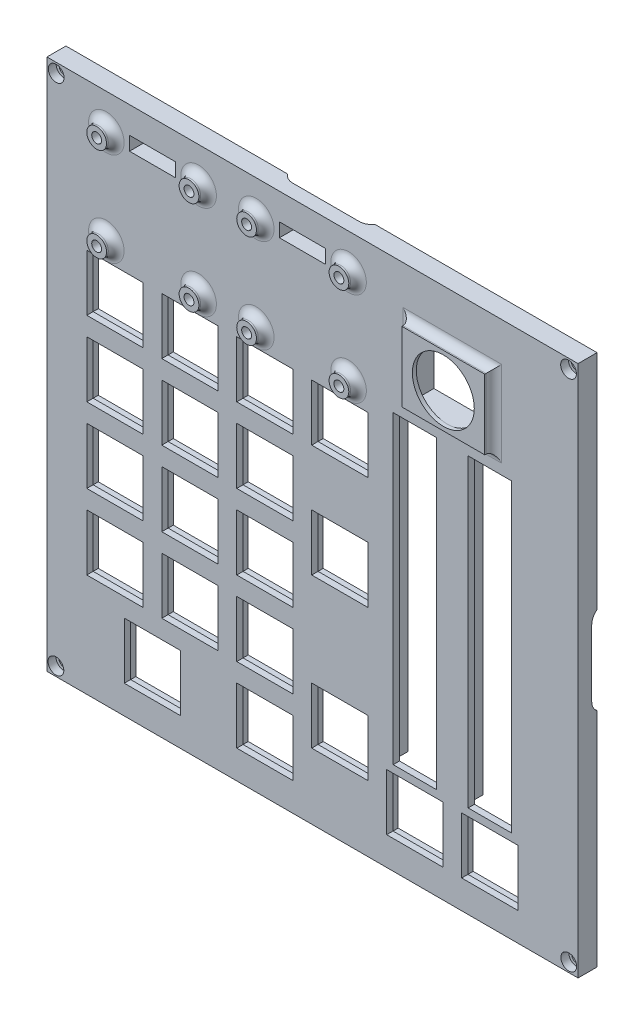
SolidWorks part; units mm, degrees
ref_plane "Front Plane" through (0, 0, 0) normal (0, 0, 1) x (1, 0, 0)
ref_plane "Top Plane" through (0, 0, 0) normal (0, 1, 0) x (1, 0, 0)
ref_plane "Right Plane" through (0, 0, 0) normal (1, 0, 0) x (0, 0, -1)
sketch "Sketch1" plane through (0, 0, 0) normal (0, 0, 1) x (1, 0, 0)
  line L0 (76.95, 30.15) -> (91.25, 30.15) construction
  line L1 (-63, 63) -> (63, 63)
  line L2 (-63, 63) -> (-63, -63)
  line L3 (-63, -63) -> (63, -63)
  line L4 (63, 63) -> (63, -63)
  line L5 (-57.15, 15.85) -> (-42.85, 15.85)
  line L6 (-57.15, 15.85) -> (-57.15, 30.15)
  line L7 (-57.15, 30.15) -> (-42.85, 30.15)
  line L8 (-42.85, 15.85) -> (-42.85, 30.15)
  line L9 (-57.15, 15.85) -> (-42.85, 30.15) construction
  line L10 (-57.15, 30.15) -> (-42.85, 15.85) construction
  line L11 (91.25, 30.15) -> (91.25, 15.85) construction
  line L12 (94.05, 32.05) -> (112.15, 32.05) construction
  line L13 (-59.05, 13.95) -> (-40.95, 13.95)
  line L14 (-59.05, 13.95) -> (-59.05, 32.05)
  line L15 (-59.05, 32.05) -> (-40.95, 32.05)
  line L16 (-40.95, 13.95) -> (-40.95, 32.05)
  line L17 (-59.05, 13.95) -> (-40.95, 32.05) construction
  line L18 (-59.05, 32.05) -> (-40.95, 13.95) construction
  line L19 (112.15, 32.05) -> (112.15, 13.95) construction
  line L20 (-38.15, 15.85) -> (-38.15, 30.15)
  line L21 (-38.15, 15.85) -> (-23.85, 15.85)
  line L22 (-38.15, 30.15) -> (-23.85, 30.15)
  line L23 (-23.85, 15.85) -> (-23.85, 30.15)
  line L24 (-40.05, 13.95) -> (-40.05, 32.05)
  line L25 (-40.05, 13.95) -> (-21.95, 13.95)
  line L26 (-21.95, 13.95) -> (-21.95, 32.05)
  line L27 (-40.05, 32.05) -> (-21.95, 32.05)
  line L28 (-19.15, 15.85) -> (-19.15, 30.15)
  line L29 (-19.15, 15.85) -> (-4.85, 15.85)
  line L30 (-19.15, 30.15) -> (-4.85, 30.15)
  line L31 (-4.85, 15.85) -> (-4.85, 30.15)
  line L32 (-21.05, 13.95) -> (-21.05, 32.05)
  line L33 (-21.05, 13.95) -> (-2.95, 13.95)
  line L34 (-2.95, 13.95) -> (-2.95, 32.05)
  line L35 (-21.05, 32.05) -> (-2.95, 32.05)
  line L36 (-38.15, -3.15) -> (-38.15, 11.15)
  line L37 (-38.15, -3.15) -> (-23.85, -3.15)
  line L38 (-38.15, 11.15) -> (-23.85, 11.15)
  line L39 (-23.85, -3.15) -> (-23.85, 11.15)
  line L40 (-40.05, -5.05) -> (-40.05, 13.05)
  line L41 (-40.05, -5.05) -> (-21.95, -5.05)
  line L42 (-21.95, -5.05) -> (-21.95, 13.05)
  line L43 (-40.05, 13.05) -> (-21.95, 13.05)
  line L44 (-19.15, -3.15) -> (-19.15, 11.15)
  line L45 (-19.15, -3.15) -> (-4.85, -3.15)
  line L46 (-19.15, 11.15) -> (-4.85, 11.15)
  line L47 (-4.85, -3.15) -> (-4.85, 11.15)
  line L48 (-21.05, -5.05) -> (-21.05, 13.05)
  line L49 (-21.05, -5.05) -> (-2.95, -5.05)
  line L50 (-2.95, -5.05) -> (-2.95, 13.05)
  line L51 (-21.05, 13.05) -> (-2.95, 13.05)
  line L52 (-38.15, -22.15) -> (-38.15, -7.85)
  line L53 (-38.15, -22.15) -> (-23.85, -22.15)
  line L54 (-38.15, -7.85) -> (-23.85, -7.85)
  line L55 (-23.85, -22.15) -> (-23.85, -7.85)
  line L56 (-40.05, -24.05) -> (-40.05, -5.95)
  line L57 (-40.05, -24.05) -> (-21.95, -24.05)
  line L58 (-21.95, -24.05) -> (-21.95, -5.95)
  line L59 (-40.05, -5.95) -> (-21.95, -5.95)
  line L60 (-19.15, -22.15) -> (-19.15, -7.85)
  line L61 (-19.15, -22.15) -> (-4.85, -22.15)
  line L62 (-19.15, -7.85) -> (-4.85, -7.85)
  line L63 (-4.85, -22.15) -> (-4.85, -7.85)
  line L64 (-21.05, -24.05) -> (-21.05, -5.95)
  line L65 (-21.05, -24.05) -> (-2.95, -24.05)
  line L66 (-2.95, -24.05) -> (-2.95, -5.95)
  line L67 (-21.05, -5.95) -> (-2.95, -5.95)
  line L68 (-38.15, -41.15) -> (-38.15, -26.85)
  line L69 (-38.15, -41.15) -> (-23.85, -41.15)
  line L70 (-38.15, -26.85) -> (-23.85, -26.85)
  line L71 (-23.85, -41.15) -> (-23.85, -26.85)
  line L72 (-40.05, -43.05) -> (-40.05, -24.95)
  line L73 (-40.05, -43.05) -> (-21.95, -43.05)
  line L74 (-21.95, -43.05) -> (-21.95, -24.95)
  line L75 (-40.05, -24.95) -> (-21.95, -24.95)
  line L76 (-19.15, -41.15) -> (-19.15, -26.85)
  line L77 (-19.15, -41.15) -> (-4.85, -41.15)
  line L78 (-19.15, -26.85) -> (-4.85, -26.85)
  line L79 (-4.85, -41.15) -> (-4.85, -26.85)
  line L80 (-21.05, -43.05) -> (-21.05, -24.95)
  line L81 (-21.05, -43.05) -> (-2.95, -43.05)
  line L82 (-2.95, -43.05) -> (-2.95, -24.95)
  line L83 (-21.05, -24.95) -> (-2.95, -24.95)
  line L84 (-57.15, -3.15) -> (-57.15, 11.15)
  line L85 (-57.15, -3.15) -> (-42.85, -3.15)
  line L86 (-57.15, 11.15) -> (-42.85, 11.15)
  line L87 (-42.85, -3.15) -> (-42.85, 11.15)
  line L88 (-59.05, -5.05) -> (-59.05, 13.05)
  line L89 (-59.05, -5.05) -> (-40.95, -5.05)
  line L90 (-40.95, -5.05) -> (-40.95, 13.05)
  line L91 (-59.05, 13.05) -> (-40.95, 13.05)
  line L92 (-57.15, -22.15) -> (-57.15, -7.85)
  line L93 (-57.15, -22.15) -> (-42.85, -22.15)
  line L94 (-57.15, -7.85) -> (-42.85, -7.85)
  line L95 (-42.85, -22.15) -> (-42.85, -7.85)
  line L96 (-59.05, -24.05) -> (-59.05, -5.95)
  line L97 (-59.05, -24.05) -> (-40.95, -24.05)
  line L98 (-40.95, -24.05) -> (-40.95, -5.95)
  line L99 (-59.05, -5.95) -> (-40.95, -5.95)
  line L100 (-57.15, -41.15) -> (-57.15, -26.85)
  line L101 (-57.15, -41.15) -> (-42.85, -41.15)
  line L102 (-57.15, -26.85) -> (-42.85, -26.85)
  line L103 (-42.85, -41.15) -> (-42.85, -26.85)
  line L104 (-59.05, -43.05) -> (-59.05, -24.95)
  line L105 (-59.05, -43.05) -> (-40.95, -43.05)
  line L106 (-40.95, -43.05) -> (-40.95, -24.95)
  line L107 (-59.05, -24.95) -> (-40.95, -24.95)
  line L108 (-19.15, -60.15) -> (-19.15, -45.85)
  line L109 (-19.15, -45.85) -> (-4.85, -45.85)
  line L110 (-4.85, -60.15) -> (-4.85, -45.85)
  line L111 (-19.15, -60.15) -> (-4.85, -60.15)
  line L112 (-21.05, -62.05) -> (-21.05, -43.95)
  line L113 (-21.05, -43.95) -> (-2.95, -43.95)
  line L114 (-2.95, -62.05) -> (-2.95, -43.95)
  line L115 (-21.05, -62.05) -> (-2.95, -62.05)
  line L116 (-0.15, 15.85) -> (-0.15, 30.15)
  line L117 (-0.15, 30.15) -> (14.15, 30.15)
  line L118 (14.15, 15.85) -> (14.15, 30.15)
  line L119 (-0.15, 15.85) -> (14.15, 15.85)
  line L120 (-2.05, 13.95) -> (-2.05, 32.05)
  line L121 (-2.05, 32.05) -> (16.05, 32.05)
  line L122 (16.05, 13.95) -> (16.05, 32.05)
  line L123 (-2.05, 13.95) -> (16.05, 13.95)
  line L124 (-0.15, -12.65) -> (-0.15, 1.65)
  line L125 (-0.15, 1.65) -> (14.15, 1.65)
  line L126 (14.15, -12.65) -> (14.15, 1.65)
  line L127 (-0.15, -12.65) -> (14.15, -12.65)
  line L128 (-2.05, -14.55) -> (-2.05, 3.55)
  line L129 (-2.05, 3.55) -> (16.05, 3.55)
  line L130 (16.05, -14.55) -> (16.05, 3.55)
  line L131 (-2.05, -14.55) -> (16.05, -14.55)
  line L132 (-0.15, -50.65) -> (-0.15, -36.35)
  line L133 (-0.15, -36.35) -> (14.15, -36.35)
  line L134 (14.15, -50.65) -> (14.15, -36.35)
  line L135 (-0.15, -50.65) -> (14.15, -50.65)
  line L136 (-2.05, -52.55) -> (-2.05, -34.45)
  line L137 (-2.05, -34.45) -> (16.05, -34.45)
  line L138 (16.05, -52.55) -> (16.05, -34.45)
  line L139 (-2.05, -52.55) -> (16.05, -52.55)
  line L140 (-47.65, -60.15) -> (-47.65, -45.85)
  line L141 (-47.65, -45.85) -> (-33.35, -45.85)
  line L142 (-33.35, -60.15) -> (-33.35, -45.85)
  line L143 (-47.65, -60.15) -> (-33.35, -60.15)
  line L144 (-49.55, -62.05) -> (-49.55, -43.95)
  line L145 (-49.55, -43.95) -> (-31.45, -43.95)
  line L146 (-31.45, -62.05) -> (-31.45, -43.95)
  line L147 (-49.55, -62.05) -> (-31.45, -62.05)
  line L148 (30, 32.3225) -> (22, 32.3225) construction
  line L149 (16.95, -62.05) -> (35.05, -62.05)
  line L150 (16.95, -62.05) -> (16.95, -43.95)
  line L151 (16.95, -43.95) -> (35.05, -43.95)
  line L152 (35.05, -62.05) -> (35.05, -43.95)
  line L153 (16.95, -62.05) -> (35.05, -43.95) construction
  line L154 (16.95, -43.95) -> (35.05, -62.05) construction
  line L155 (18.85, -60.15) -> (33.15, -60.15)
  line L156 (18.85, -60.15) -> (18.85, -45.85)
  line L157 (18.85, -45.85) -> (33.15, -45.85)
  line L158 (33.15, -60.15) -> (33.15, -45.85)
  line L159 (18.85, -60.15) -> (33.15, -45.85) construction
  line L160 (18.85, -45.85) -> (33.15, -60.15) construction
  line L161 (35.95, -62.05) -> (54.05, -62.05)
  line L162 (35.95, -62.05) -> (35.95, -43.95)
  line L163 (35.95, -43.95) -> (54.05, -43.95)
  line L164 (54.05, -62.05) -> (54.05, -43.95)
  line L165 (35.95, -62.05) -> (54.05, -43.95) construction
  line L166 (35.95, -43.95) -> (54.05, -62.05) construction
  line L167 (37.85, -60.15) -> (52.15, -60.15)
  line L168 (37.85, -60.15) -> (37.85, -45.85)
  line L169 (37.85, -45.85) -> (52.15, -45.85)
  line L170 (52.15, -60.15) -> (52.15, -45.85)
  line L171 (37.85, -60.15) -> (52.15, -45.85) construction
  line L172 (37.85, -45.85) -> (52.15, -60.15) construction
  line L173 (20.5, 33.3225) -> (31.5, 33.3225)
  line L174 (20.5, 33.3225) -> (20.5, -43.95)
  line L175 (20.5, -43.95) -> (31.5, -43.95)
  line L176 (31.5, 33.3225) -> (31.5, -43.95)
  line L177 (-45.83, 60.275) -> (-35.17, 60.275) construction
  line L178 (30.5, -10.1622) -> (30.5, -27.0779) construction
  line L179 (21.5, -10.1622) -> (21.5, -27.0779) construction
  line L180 (49, 32.3225) -> (41, 32.3225) construction
  line L181 (39.5, 33.3225) -> (50.5, 33.3225)
  line L182 (39.5, 33.3225) -> (39.5, -43.95)
  line L183 (39.5, -43.95) -> (50.5, -43.95)
  line L184 (50.5, 33.3225) -> (50.5, -43.95)
  line L185 (40.5, 30.2991) -> (40.5, 31.8225) construction
  line L186 (49.5, 31.8225) -> (49.5, 30.2991) construction
  line L187 (-46.33, 60.775) -> (-34.67, 60.775)
  line L188 (27, 50.3) -> (27, 48.3) construction
  line L189 (26, 38.95) -> (45, 38.95)
  line L190 (26, 38.95) -> (26, 54.65)
  line L191 (26, 54.65) -> (45, 54.65)
  line L192 (45, 38.95) -> (45, 54.65)
  line L193 (26, 38.95) -> (45, 54.65) construction
  line L194 (26, 54.65) -> (45, 38.95) construction
  line L195 (37, 53.65) -> (34, 53.65) construction
  line L196 (19.5, 34.3225) -> (32.5, 34.3225)
  line L197 (19.5, 34.3225) -> (19.5, -43.95)
  line L198 (19.5, -43.95) -> (32.5, -43.95)
  line L199 (32.5, 34.3225) -> (32.5, -43.95)
  line L200 (38.5, 34.3225) -> (51.5, 34.3225)
  line L201 (38.5, 34.3225) -> (38.5, -43.95)
  line L202 (38.5, -43.95) -> (51.5, -43.95)
  line L203 (51.5, 34.3225) -> (51.5, -43.95)
  line L204 (-46.33, 60.775) -> (-46.33, 57.275)
  line L205 (-46.33, 57.275) -> (-34.67, 57.275)
  line L206 (-34.67, 60.775) -> (-34.67, 57.275)
  line L207 (-8.33, 60.775) -> (3.33, 60.775)
  line L208 (-8.33, 60.775) -> (-8.33, 57.275)
  line L209 (-8.33, 57.275) -> (3.33, 57.275)
  line L210 (3.33, 60.775) -> (3.33, 57.275)
  line L211 (-45.83, 57.775) -> (-35.17, 57.775) construction
  line L212 (-35.17, 60.025) -> (-35.17, 58.025) construction
  line L213 (-45.83, 60.025) -> (-45.83, 58.025) construction
  line L214 (2.83, 60.025) -> (2.83, 58.025) construction
  line L215 (-7.83, 60.275) -> (2.83, 60.275) construction
  line L216 (-7.83, 60.025) -> (-7.83, 58.025) construction
  line L217 (-7.83, 57.775) -> (2.83, 57.775) construction
  circle A0 centre (-50, 23) radius 1.1145 construction
  circle A1 centre (26, -53) radius 1.1245 construction
  circle A2 centre (45, -53) radius 1.0254 construction
  circle A3 centre (35.5, 46.8) radius 3.3 construction
  circle A4 centre (35.5, 46.8) radius 3.3 construction
  circle A5 centre (35.5, 46.8) radius 7.85
  circle A6 centre (-52.2, 58.5) radius 1.25
  circle A7 centre (-28.8, 58.5) radius 1.25
  circle A8 centre (-52.2, 34.7) radius 1.25
  circle A9 centre (-28.8, 34.7) radius 1.25
  circle A10 centre (-14.2, 34.7) radius 1.25
  circle A11 centre (-14.2, 58.5) radius 1.25
  circle A12 centre (9.2, 58.5) radius 1.25
  circle A13 centre (9.2, 34.7) radius 1.25
  ellipse E0 centre (26, -53) end of major axis (27.995, -53) minor radius 1.995 construction
  ellipse E1 centre (-50, 23) end of major axis (-50, 21.005) minor radius 1.995 construction
  ellipse E2 centre (45, -53) end of major axis (45, -54.995) minor radius 1.995 construction
  ellipse E3 centre (-52.2, 58.5) end of major axis (-52.2, 57.5) minor radius 1 construction
  ellipse E4 centre (-52.2, 34.7) end of major axis (-52.2, 33.7) minor radius 1 construction
  ellipse E5 centre (-28.8, 34.7) end of major axis (-28.8, 33.7) minor radius 1 construction
  ellipse E6 centre (-14.2, 58.5) end of major axis (-14.2, 57.5) minor radius 1 construction
  ellipse E7 centre (9.2, 58.5) end of major axis (9.2, 57.5) minor radius 1 construction
  ellipse E8 centre (9.2, 34.7) end of major axis (9.2, 33.7) minor radius 1 construction
  ellipse E9 centre (-14.2, 34.7) end of major axis (-14.2, 33.7) minor radius 1 construction
  ellipse E10 centre (-28.8, 58.5) end of major axis (-28.8, 57.5) minor radius 1 construction
  point P212 (35.5, 46.8)
  dimension "D23" = 15.7
  dimension "D38" = 2.5
  dimension "D3" = 19
  dimension "D4" = 19
  dimension "D6" = 19
  dimension "D8" = 19
  dimension "D10" = 28.5
  dimension "D12" = 38
  dimension "D14" = 28.5
  dimension "D15" = 1
  dimension "D16" = 1
  dimension "D17" = 1
  dimension "D18" = 1
  dimension "D19" = 1
  dimension "D20" = 1
  dimension "D21" = 1
  dimension "D22" = 1
  dimension "D24" = 1
  dimension "D25" = 1
  dimension "D26" = 1
  dimension "D27" = 1
  dimension "D28" = 1
  dimension "D29" = 1
  dimension "D30" = 0.5
  dimension "D31" = 0.5
  dimension "D32" = 0.5
  dimension "D33" = 0.5
  dimension "D34" = 0.5
  dimension "D35" = 0.5
  dimension "D36" = 0.5
  dimension "D37" = 0.5
  dimension "D1" = 3
  dimension "D2" = 4
  dimension "D5" = 2
  dimension "D7" = 2
  dimension "D9" = 2
  dimension "D11" = 2
  dimension "D13" = 2
extrude "Boss-Extrude1" add sketch "Sketch1" along normal up to surface (3.2116 mm away) contours L4 L1 L2 L3 L192 L189 L190 L191 L147 L144 L145 L146 L139 L136 L137 L138 L131 L128 L129 L130 L123 L120 L121 L122 L115 L112 L113 L114 L96 L99 L98 L97 L80 L83 L82 L81 L64 L67 L66 L65 region at (3.9869, 12.3357, 0)
extrude "Boss-Extrude2" add sketch "Sketch1<4>" along normal up to surface (1.6 mm away) from surface contours L4 L1 L2 L3 L192 L189 L190 L191 L147 L144 L145 L146 L139 L136 L137 L138 L131 L128 L129 L130 L123 L120 L121 L122 L115 L112 L113 L114 L96 L99 L98 L97 L80 L83 L82 L81 L64 L67 L66 L65 | L120 L123 L122 L121 L119 L116 L117 L118 | L27 L24 L25 L26 L23 L21 L20 L22 | L43 L40 L41 L42 L39 L37 L36 L38 | L51 L48 L49 L50 L47 L45 L44 L46 | L35 L32 L33 L34 L31 L29 L28 L30 | L91 L88 L89 L90 L87 L85 L84 L86 | L13 L16 L15 L14 L8 L5 L6 L7 | L59 L56 L57 L58 L55 L53 L52 L54 | L99 L96 L97 L98 L95 L93 L92 L94 | L67 L64 L65 L66 L63 L61 L60 L62 | L107 L104 L105 L106 L103 L101 L100 L102 | L75 L72 L73 L74 L71 L69 L68 L70 | L83 L80 L81 L82 L79 L77 L76 L78 | L144 L147 L146 L145 L143 L140 L141 L142 | L112 L115 L114 L113 L111 L108 L109 L110 | L136 L139 L138 L137 L135 L132 L133 L134 | L128 L131 L130 L129 L127 L124 L125 L126 | L149 L152 L151 L150 L158 L155 L156 L157 | L161 L164 L163 L162 L170 L167 L168 L169 | L199 L196 L197 L151 L174 L173 L176 | L203 L200 L201 L163 L182 L181 L184 region at (3.9869, 12.3357, 0) region at (-58.794, 23, 0) region at (-39.794, 23, 0) region at (-20.794, 23, 0) region at (-39.794, 4, 0) region at (-20.794, 4, 0) region at (-39.794, -15, 0) region at (-20.794, -15, 0) region at (-39.794, -34, 0) region at (-20.794, -34, 0) region at (-58.794, 4, 0) region at (-58.794, -15, 0) region at (-58.794, -34, 0) region at (-20.794, -53, 0) region at (-1.794, 23, 0) region at (-1.794, -5.5, 0) region at (-1.794, -43.5, 0) region at (-49.294, -53, 0) region at (17.206, -53, 0) region at (20.2934, -4.8138, 0) region at (36.206, -53, 0) region at (39.2934, -4.8138, 0) starting at face at (-50, 23, 3.2116)
sketch "Sketch1<4>" plane through (0, 0, 0) normal (0, 0, 1) x (1, 0, 0) same geometry as "Sketch1"
sketch "Sketch3" plane through (0, 0, 4.8116) normal (0, 0, 1) x (1, 0, 0)
  circle A0 centre (-52.2, 58.5) radius 1.25
  circle A1 centre (-52.2, 34.7) radius 1.25
  circle A2 centre (-28.8, 34.7) radius 1.25
  circle A3 centre (-14.2, 34.7) radius 1.25
  circle A4 centre (-28.8, 58.5) radius 1.25
  circle A5 centre (-14.2, 58.5) radius 1.25
  circle A6 centre (9.2, 58.5) radius 1.25
  circle A7 centre (9.2, 34.7) radius 1.25
  circle A8 centre (-52.2, 58.5) radius 1.25 construction
  circle A9 centre (-52.2, 34.7) radius 1.25 construction
  circle A10 centre (-28.8, 58.5) radius 1.25 construction
  circle A11 centre (-14.2, 58.5) radius 1.25 construction
  circle A12 centre (-28.8, 34.7) radius 1.25 construction
  circle A13 centre (-14.2, 34.7) radius 1.25 construction
  circle A14 centre (9.2, 34.7) radius 1.25 construction
  circle A15 centre (9.2, 58.5) radius 1.25 construction
  circle A16 centre (-52.2, 58.5) radius 2.5
  circle A17 centre (-28.8, 58.5) radius 2.5
  circle A18 centre (-14.2, 58.5) radius 2.5
  circle A19 centre (9.2, 58.5) radius 2.5
  circle A20 centre (-52.2, 34.7) radius 2.5
  circle A21 centre (-28.8, 34.7) radius 2.5
  circle A22 centre (-14.2, 34.7) radius 2.5
  circle A23 centre (9.2, 34.7) radius 2.5
  dimension "D1" = 5
extrude "Boss-Extrude3" add sketch "Sketch3" along normal up to surface (2.4544 mm away)
fillet "Fillet1" radius 2 8 edges at (-54.7, 34.7, 4.8116) (-31.3, 34.7, 4.8116) (-16.7, 34.7, 4.8116) (6.7, 58.5, 4.8116) (6.7, 34.7, 4.8116) (-16.7, 58.5, 4.8116) (-31.3, 58.5, 4.8116) (-54.7, 58.5, 4.8116)
sketch "Sketch4" plane through (0, 0, 4.8116) normal (0, 0, 1) x (1, 0, 0)
  line L1 (25, 55.65) -> (46, 55.65)
  line L2 (25, 55.65) -> (25, 37.95)
  line L3 (25, 37.95) -> (46, 37.95)
  line L4 (46, 55.65) -> (46, 37.95)
  line L5 (26, 54.65) -> (45, 54.65)
  line L6 (26, 54.65) -> (26, 38.95)
  line L7 (26, 38.95) -> (45, 38.95)
  line L8 (45, 54.65) -> (45, 38.95)
  dimension "D1" = 1
  dimension "D2" = 1
  dimension "D3" = 1
  dimension "D4" = 1
extrude "Boss-Extrude4" add sketch "Sketch4" along normal blind 2.3
extrude "Boss-Extrude5" add sketch "Sketch1<6>" against normal blind 1 from surface contours A5 L191 L190 L189 | A5 L189 L192 L191 region at (26.1835, 46.8, 0) region at (41.1805, 41.1195, 0) starting at face at (35.5, 46.8, 7.1116)
sketch "Sketch1<6>" plane through (0, 0, 0) normal (0, 0, 1) x (1, 0, 0) same geometry as "Sketch1"
fillet "Fillet2" radius 2 4 edges at (25, 46.8, 4.8116) (35.5, 55.65, 4.8116) (46, 46.8, 4.8116) (35.5, 37.95, 4.8116)
sketch "Sketch5" plane through (-63, 0, 0) normal (-1, 0, 0) x (0, 0, 1)
  line L0 (-2, 8.5) -> (-2, -8.5) construction
  line L1 (3, 8.5) -> (3, -8.5)
  line L2 (-7, 8.5) -> (-7, -8.5)
  line L3 (2, 8.5) -> (2, -8.5) construction
  line L4 (-6, -8.5) -> (-6, 8.5) construction
  line L6 (4.8116, 63) -> (0, 63)
  line L7 (4.8116, 63) -> (4.8116, -63)
  line L8 (4.8116, -63) -> (0, -63)
  line L9 (0, 63) -> (0, -63)
  arc A0 (3, 8.5) -> (-7, 8.5) centre (-2, 8.5) ccw
  arc A1 (-7, -8.5) -> (3, -8.5) centre (-2, -8.5) ccw
  arc A2 (2, 8.5) -> (-6, 8.5) centre (-2, 8.5) ccw construction
  point P2 (-2, 0)
  point P14 (-2, 12.5)
  point P15 (-2, 13.5)
  point P17 (-2, -13.5)
  line M3 (0, -63) -> (4.8116, -63)
  line M4 (4.8116, -63) -> (4.8116, 63)
  line M5 (4.8116, 63) -> (0, 63)
  line M6 (0, 63) -> (0, -63)
  dimension "D1" = 1
  dimension "D2" = 1
  dimension "D3" = 1
  dimension "D4" = 1
extrude "Boss-Extrude6" add sketch "Sketch5" along normal up to surface (3.45 mm away) contours A1 A0 L1 M6 M3 M4 M5 region at (-63, 11.9292, 3.2383) up to face at (63, 0, 2.4058)
sketch "Sketch6" plane through (0, -63, 0) normal (0, -1, 0) x (1, 0, 0)
  line L0 (-8.5, -2) -> (8.5, -2) construction
  line L1 (-8.5, 3) -> (8.5, 3)
  line L2 (-8.5, -7) -> (8.5, -7)
  line L3 (-8.5, 2) -> (8.5, 2) construction
  line L4 (8.5, -6) -> (-8.5, -6) construction
  line L5 (-66.45, 0) -> (63, 0) construction
  line L6 (-66.45, 4.8116) -> (63, 4.8116)
  line L7 (-66.45, 4.8116) -> (-66.45, 0)
  line L8 (-66.45, 0) -> (63, 0)
  line L9 (63, 4.8116) -> (63, 0)
  arc A0 (-8.5, 3) -> (-8.5, -7) centre (-8.5, -2) ccw
  arc A1 (8.5, -7) -> (8.5, 3) centre (8.5, -2) ccw
  arc A2 (-8.5, 2) -> (-8.5, -6) centre (-8.5, -2) ccw construction
  point P2 (0, -2)
  point P12 (13.5, -2)
  point P16 (-12.5, -2)
  point P17 (-13.5, -2)
  line M3 (63, 0) -> (63, 4.8116)
  line M4 (63, 4.8116) -> (-66.45, 4.8116)
  line M5 (-66.45, 4.8116) -> (-66.45, 0)
  line M6 (-66.45, 0) -> (63, 0)
  dimension "D1" = 1
  dimension "D2" = 1
  dimension "D3" = 1
  dimension "D4" = 1
extrude "Boss-Extrude7" add sketch "Sketch6" along normal up to surface (3.55 mm away) contours A1 A0 L1 M6 M3 M4 M5 region at (-11.9481, -63, 3.2671)
sketch "Sketch7" plane through (63, 0, 0) normal (1, 0, 0) x (0, 0, -1)
  line L0 (2, -8.5) -> (2, 8.5) construction
  line L1 (-3, -8.5) -> (-3, 8.5)
  line L2 (7, -8.5) -> (7, 8.5)
  line L3 (-2, -8.5) -> (-2, 8.5) construction
  line L4 (6, 8.5) -> (6, -8.5) construction
  line L6 (-4.8116, -66.55) -> (0, -66.55)
  line L7 (-4.8116, -66.55) -> (-4.8116, 63)
  line L8 (-4.8116, 63) -> (0, 63)
  line L9 (0, -66.55) -> (0, 63)
  arc A0 (-3, -8.5) -> (7, -8.5) centre (2, -8.5) ccw
  arc A1 (7, 8.5) -> (-3, 8.5) centre (2, 8.5) ccw
  arc A2 (-2, -8.5) -> (6, -8.5) centre (2, -8.5) ccw construction
  point P2 (2, 0)
  point P12 (2, 13.5)
  point P16 (2, -12.5)
  point P17 (2, -13.5)
  line M3 (0, 63) -> (-4.8116, 63)
  line M4 (-4.8116, 63) -> (-4.8116, -66.55)
  line M5 (-4.8116, -66.55) -> (0, -66.55)
  line M6 (0, -66.55) -> (0, 63)
  dimension "D1" = 1
  dimension "D2" = 1
  dimension "D3" = 1
  dimension "D4" = 1
extrude "Boss-Extrude8" add sketch "Sketch7" along normal up to surface (3.55 mm away) contours A1 A0 L1 M6 M3 M4 M5 region at (63, -11.9487, 3.2679)
sketch "Sketch8" plane through (0, 63, 0) normal (0, 1, 0) x (1, 0, 0)
  line L0 (8.5, 2) -> (-8.5, 2) construction
  line L1 (8.5, -3) -> (-8.5, -3)
  line L2 (8.5, 7) -> (-8.5, 7)
  line L3 (8.5, -2) -> (-8.5, -2) construction
  line L4 (-8.5, 6) -> (8.5, 6) construction
  line L6 (66.55, -4.8116) -> (-66.45, -4.8116)
  line L7 (66.55, -4.8116) -> (66.55, 0)
  line L8 (66.55, 0) -> (-66.45, 0)
  line L9 (-66.45, -4.8116) -> (-66.45, 0)
  arc A0 (8.5, -3) -> (8.5, 7) centre (8.5, 2) ccw
  arc A1 (-8.5, 7) -> (-8.5, -3) centre (-8.5, 2) ccw
  arc A2 (8.5, -2) -> (8.5, 6) centre (8.5, 2) ccw construction
  point P2 (0, 2)
  point P12 (-13.5, 2)
  point P16 (12.5, 2)
  point P17 (13.5, 2)
  line M3 (66.55, 0) -> (-66.45, 0)
  line M4 (-66.45, 0) -> (-66.45, -4.8116)
  line M5 (-66.45, -4.8116) -> (-52.2, -4.8116)
  line M6 (-52.2, -4.8116) -> (-28.8, -4.8116)
  line M7 (-28.8, -4.8116) -> (-14.2, -4.8116)
  line M8 (-14.2, -4.8116) -> (9.2, -4.8116)
  line M9 (9.2, -4.8116) -> (66.55, -4.8116)
  line M10 (66.55, -4.8116) -> (66.55, 0)
  dimension "D1" = 1
  dimension "D2" = 1
  dimension "D3" = 1
  dimension "D4" = 1
extrude "Boss-Extrude9" add sketch "Sketch8" along normal up to surface (3.7 mm away) contours A1 A0 L1 M3 M4 M5 M6 M7 M8 M9 M10 region at (11.9676, 63, 3.2968)
sketch "Sketch9" plane through (-66.45, 0, 0) normal (-1, 0, 0) x (0, 0, 1)
  line L0 (-2, 8.4) -> (-2, -8.4) construction
  line L1 (1.35, 8.4) -> (1.35, -8.4)
  line L2 (-5.35, 8.4) -> (-5.35, -8.4)
  line L3 (0.85, 8.4) -> (0.85, -8.4) construction
  line L4 (-4.85, -8.4) -> (-4.85, 8.4) construction
  line L6 (4.8116, 66.7) -> (0, 66.7)
  line L7 (4.8116, 66.7) -> (4.8116, -66.55)
  line L8 (4.8116, -66.55) -> (0, -66.55)
  line L9 (0, 66.7) -> (0, -66.55)
  arc A0 (1.35, 8.4) -> (-5.35, 8.4) centre (-2, 8.4) ccw
  arc A1 (-5.35, -8.4) -> (1.35, -8.4) centre (-2, -8.4) ccw
  arc A2 (-4.85, -8.4) -> (0.85, -8.4) centre (-2, -8.4) ccw construction
  point P2 (-2, 0)
  point P14 (-2, -11.25)
  point P15 (-2, -11.75)
  point P17 (-2, 11.75)
  arc M3 (3, -8.5) -> (0, -13.0826) centre (-2, -8.5) cw
  line M4 (0, -13.0826) -> (0, -66.55)
  line M5 (0, -66.55) -> (4.8116, -66.55)
  line M6 (4.8116, -66.55) -> (4.8116, 66.7)
  line M7 (4.8116, 66.7) -> (0, 66.7)
  line M8 (0, 66.7) -> (0, 13.0826)
  arc M9 (0, 13.0826) -> (3, 8.5) centre (-2, 8.5) cw
  line M10 (3, 8.5) -> (3, -8.5)
  dimension "D1" = 0.5
  dimension "D2" = 0.5
  dimension "D3" = 0.5
  dimension "D4" = 0.5
extrude "Boss-Extrude10" add sketch "Sketch9" along normal up to surface (0.8 mm away) contours M10 M3 M4 M5 M6 M7 M8 M9 | A1 L9 A0 L1 M3 M10 M9 region at (-66.45, 0, 1.9255) region at (-66.45, 39.8913, 1.3334) up to face at (63, 0, 1.8417)
sketch "Sketch10" plane through (0, -66.55, 0) normal (0, -1, 0) x (1, 0, 0)
  line L0 (-8.4, -2) -> (8.4, -2) construction
  line L1 (-8.4, 1.35) -> (8.4, 1.35)
  line L2 (-8.4, -5.35) -> (8.4, -5.35)
  line L3 (-8.4, 0.85) -> (8.4, 0.85) construction
  line L4 (8.4, -4.85) -> (-8.4, -4.85) construction
  line L7 (-67.25, 4.8116) -> (66.55, 4.8116)
  line L8 (-67.25, 4.8116) -> (-67.25, 0)
  line L9 (-67.25, 0) -> (66.55, 0)
  line L10 (66.55, 4.8116) -> (66.55, 0)
  arc A0 (-8.4, 1.35) -> (-8.4, -5.35) centre (-8.4, -2) ccw
  arc A1 (8.4, -5.35) -> (8.4, 1.35) centre (8.4, -2) ccw
  arc A2 (8.4, -4.85) -> (8.4, 0.85) centre (8.4, -2) ccw construction
  point P2 (0, -2)
  point P12 (-11.75, -2)
  point P16 (11.25, -2)
  point P17 (11.75, -2)
  arc M3 (8.5, 3) -> (13.0826, 0) centre (8.5, -2) cw
  line M4 (13.0826, 0) -> (66.55, 0)
  line M5 (66.55, 0) -> (66.55, 4.8116)
  line M6 (66.55, 4.8116) -> (-67.25, 4.8116)
  line M7 (-67.25, 4.8116) -> (-67.25, 0)
  line M8 (-67.25, 0) -> (-13.0826, 0)
  arc M9 (-13.0826, 0) -> (-8.5, 3) centre (-8.5, -2) cw
  line M10 (-8.5, 3) -> (8.5, 3)
  dimension "D1" = 0.5
  dimension "D2" = 0.5
  dimension "D3" = 0.5
  dimension "D4" = 0.5
extrude "Boss-Extrude11" add sketch "Sketch10" along normal up to surface (0.8 mm away) contours M10 M3 M4 M5 M6 M7 M8 M9 | A1 L9 A0 L1 M3 M10 M9 region at (0, -66.55, 1.9255) region at (-40.1663, -66.55, 1.3389)
sketch "Sketch11" plane through (66.55, 0, 0) normal (1, 0, 0) x (0, 0, -1)
  line L0 (2, -8.4) -> (2, 8.4) construction
  line L1 (-1.35, -8.4) -> (-1.35, 8.4)
  line L2 (5.35, -8.4) -> (5.35, 8.4)
  line L3 (-0.85, -8.4) -> (-0.85, 8.4) construction
  line L4 (4.85, 8.4) -> (4.85, -8.4) construction
  line L6 (-4.8116, -67.35) -> (0, -67.35)
  line L7 (-4.8116, -67.35) -> (-4.8116, 66.7)
  line L8 (-4.8116, 66.7) -> (0, 66.7)
  line L9 (0, -67.35) -> (0, 66.7)
  arc A0 (-1.35, -8.4) -> (5.35, -8.4) centre (2, -8.4) ccw
  arc A1 (5.35, 8.4) -> (-1.35, 8.4) centre (2, 8.4) ccw
  arc A2 (4.85, 8.4) -> (-0.85, 8.4) centre (2, 8.4) ccw construction
  point P2 (2, 0)
  point P12 (2, -11.75)
  point P16 (2, 11.25)
  point P17 (2, 11.75)
  arc M3 (-3, 8.5) -> (0, 13.0826) centre (2, 8.5) cw
  line M4 (0, 13.0826) -> (0, 66.7)
  line M5 (0, 66.7) -> (-4.8116, 66.7)
  line M6 (-4.8116, 66.7) -> (-4.8116, -67.35)
  line M7 (-4.8116, -67.35) -> (0, -67.35)
  line M8 (0, -67.35) -> (0, -13.0826)
  arc M9 (0, -13.0826) -> (-3, -8.5) centre (2, -8.5) cw
  line M10 (-3, -8.5) -> (-3, 8.5)
  dimension "D1" = 0.5
  dimension "D2" = 0.5
  dimension "D3" = 0.5
  dimension "D4" = 0.5
extrude "Boss-Extrude12" add sketch "Sketch11" along normal up to surface (0.8 mm away) contours M10 M3 M4 M5 M6 M7 M8 M9 | A1 L9 A0 L1 M3 M10 M9 region at (66.55, 0, 1.9255) region at (66.55, -40.2163, 1.3414)
sketch "Sketch12" plane through (0, 66.7, 0) normal (0, 1, 0) x (1, 0, 0)
  line L0 (8.4, 2) -> (-8.4, 2) construction
  line L1 (8.4, -1.35) -> (-8.4, -1.35)
  line L2 (8.4, 5.35) -> (-8.4, 5.35)
  line L3 (8.4, -0.85) -> (-8.4, -0.85) construction
  line L4 (-8.4, 4.85) -> (8.4, 4.85) construction
  line L6 (67.35, -4.8116) -> (-67.25, -4.8116)
  line L7 (67.35, -4.8116) -> (67.35, 0)
  line L8 (67.35, 0) -> (-67.25, 0)
  line L9 (-67.25, -4.8116) -> (-67.25, 0)
  arc A0 (8.4, -1.35) -> (8.4, 5.35) centre (8.4, 2) ccw
  arc A1 (-8.4, 5.35) -> (-8.4, -1.35) centre (-8.4, 2) ccw
  arc A2 (-8.4, 4.85) -> (-8.4, -0.85) centre (-8.4, 2) ccw construction
  point P2 (0, 2)
  point P12 (11.75, 2)
  point P16 (-11.25, 2)
  point P17 (-11.75, 2)
  arc M3 (-8.5, -3) -> (-13.0826, 0) centre (-8.5, 2) cw
  line M4 (-13.0826, 0) -> (-67.25, 0)
  line M5 (-67.25, 0) -> (-67.25, -4.8116)
  line M6 (-67.25, -4.8116) -> (67.35, -4.8116)
  line M7 (67.35, -4.8116) -> (67.35, 0)
  line M8 (67.35, 0) -> (13.0826, 0)
  arc M9 (13.0826, 0) -> (8.5, -3) centre (8.5, 2) cw
  line M10 (8.5, -3) -> (-8.5, -3)
  dimension "D1" = 0.5
  dimension "D2" = 0.5
  dimension "D3" = 0.5
  dimension "D4" = 0.5
extrude "Boss-Extrude13" add sketch "Sketch12" along normal up to surface (0.8 mm away) contours M10 M3 M4 M5 M6 M7 M8 M9 | A1 L8 A0 L1 M3 M10 M9 region at (0, 66.7, 1.9255) region at (40.2163, 66.7, 1.3469)
sketch "Sketch13" plane through (0, 0, 0) normal (0, 0, -1) x (-1, 0, 0)
  circle A0 centre (-64.9354, 65.0565) radius 1.25
  circle A1 centre (-64.9354, 65.0565) radius 1.8 construction
  circle A2 centre (-64.9971, -64.9971) radius 1.25
  circle A3 centre (-64.9971, -64.9971) radius 1.8 construction
  circle A4 centre (64.9757, -65.0181) radius 1.25
  circle A5 centre (64.9757, -65.0181) radius 1.8 construction
  circle A6 centre (64.9134, 65.0768) radius 1.25
  circle A7 centre (64.9134, 65.0768) radius 1.8 construction
  dimension "D1" = 2.5
extrude "Cut-Extrude1" cut sketch "Sketch13" against normal up to surface (4.8116 mm away) up to face at (10.45, 34.7, 0)
sketch "Sketch14" plane through (0, 0, 4.8116) normal (0, 0, 1) x (1, 0, 0)
  circle A0 centre (-64.9757, -65.0181) radius 2
  circle A1 centre (-64.9757, -65.0181) radius 1.25 construction
  circle A2 centre (64.9971, -64.9971) radius 2
  circle A3 centre (64.9354, 65.0565) radius 2
  circle A4 centre (-64.9134, 65.0768) radius 2
  circle A5 centre (64.9971, -64.9971) radius 1.25 construction
  dimension "D1" = 4
extrude "Cut-Extrude2" cut sketch "Sketch14" against normal blind 2
